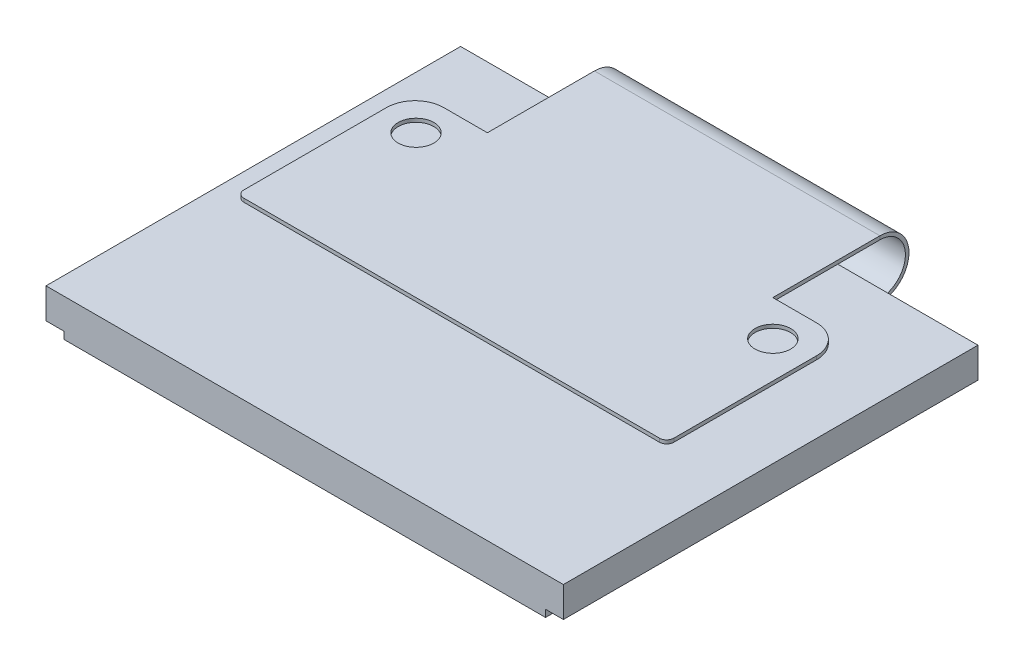
SolidWorks part; units mm, degrees
ref_plane "Front Plane" through (0, 0, 0) normal (0, 0, 1) x (1, 0, 0)
ref_plane "Top Plane" through (0, 0, 0) normal (0, 1, 0) x (1, 0, 0)
ref_plane "Right Plane" through (0, 0, 0) normal (1, 0, 0) x (0, 0, -1)
sketch "Sketch2" plane through (0, 0, 0) normal (0, 1, 0) x (1, 0, 0)
  line L1 (-7.25, 5.81) -> (7.25, 5.81)
  line L2 (-7.25, 5.81) -> (-7.25, -5.81)
  line L3 (-7.25, -5.81) -> (7.25, -5.81)
  line L4 (7.25, 5.81) -> (7.25, -5.81)
  line L5 (-7.25, 5.81) -> (7.25, -5.81) construction
  line L6 (-7.25, -5.81) -> (7.25, 5.81) construction
  point P0 (0, 0)
extrude "Boss-Extrude1" add sketch "Sketch2" along normal mid plane 0.85
sketch "Sketch6" plane through (0, -0.425, 0) normal (0, -1, 0) x (1, 0, 0)
  line L0 (-7.25, 5.81) -> (7.25, 5.81) construction
  line L1 (-6.75, 5.81) -> (6.75, 5.81)
  line L2 (-6.75, 5.81) -> (-6.75, -2.29)
  line L3 (-6.75, -2.29) -> (6.75, -2.29)
  line L4 (6.75, 5.81) -> (6.75, -2.29)
  line L5 (-6.75, 5.81) -> (6.75, -2.29) construction
  line L6 (-6.75, -2.29) -> (6.75, 5.81) construction
  point P0 (0, 1.76)
  dimension "D1" = 0
  dimension "D2" = 0
  dimension "D3" = 8.1
  dimension "D4" = 13.5
extrude "Boss-Extrude2" add sketch "Sketch6" along normal blind 0.2
sketch "Sketch7" plane through (0, -0.625, 0) normal (0, -1, 0) x (1, 0, 0)
  line L0 (6.75, 5.81) -> (-6.75, 5.81) construction
  line L1 (-6.29, 5) -> (6.29, 5)
  line L2 (-6.29, 5) -> (-6.29, -1.98)
  line L3 (-6.29, -1.98) -> (6.29, -1.98)
  line L4 (6.29, 5) -> (6.29, -1.98)
  line L5 (-6.29, 5) -> (6.29, -1.98) construction
  line L6 (-6.29, -1.98) -> (6.29, 5) construction
  line L7 (-6.75, 5.81) -> (-6.75, -2.29) construction
  line L8 (-6.75, -2.29) -> (6.75, -2.29) construction
  point P0 (0, 1.51)
  dimension "D1" = 0.81
  dimension "D2" = 0
  dimension "D3" = 0.46
  dimension "D4" = 0.31
extrude "Boss-Extrude3" add sketch "Sketch7" along normal blind 0.15
sketch "Sketch9" plane through (0, -0.425, 0) normal (0, -1, 0) x (1, 0, 0)
  line L1 (-6.096, -2.4527) -> (6.096, -2.4527)
  line L2 (-6.096, -2.4527) -> (-6.096, -4.9927)
  line L3 (-6.096, -4.9927) -> (-3.2893, -4.9927)
  line L4 (6.096, -2.4527) -> (6.096, -4.9927)
  line L5 (-6.096, -2.4527) -> (6.096, -4.9927) construction
  line L6 (-6.096, -4.9927) -> (6.096, -2.4527) construction
  line L7 (-6.75, -2.29) -> (6.75, -2.29) construction
  line L8 (-3.2893, -7.8563) -> (3.2893, -7.8563)
  line L9 (-3.2893, -4.9927) -> (-3.2893, -7.8563)
  line L10 (0, 0) -> (0, -4.9927) construction
  line L11 (3.2893, -4.9927) -> (3.2893, -7.8563)
  line L12 (3.2893, -4.9927) -> (6.096, -4.9927)
  line L13 (0, -7.8563) -> (0, -11.701) construction
  point P0 (0, -3.7227)
  point P11 (0, -7.8563)
  dimension "D1" = 0.1627
  dimension "D2" = 12.192
  dimension "D3" = 0
  dimension "D4" = 2.54
  dimension "D5" = 2.8636
  dimension "D6" = 6.5786
extrude "Boss-Extrude4" add sketch "Sketch9" along normal blind 0.1755
fillet "Fillet1" radius 0.762 2 edges at (6.096, -0.5127, -4.9927) (-6.096, -0.5127, -4.9927)
fillet "Fillet2" radius 0.2 2 edges at (3.2893, -0.5127, -7.8563) (-3.2893, -0.5127, -7.8563)
sketch "Sketch12" plane through (0, 0, 0) normal (1, 0, 0) x (0, 0, -1)
  line L0 (5.81, -0.425) -> (6.31, -0.425)
  line L2 (6.31, 1.205) -> (-1.69, 1.205)
  arc A1 (6.31, -0.425) -> (6.31, 1.205) centre (6.31, 0.39) ccw
  point P3 (7.125, 0.39)
  point P7 (6.31, 1.205)
  dimension "D2" = 1.63
  dimension "D3" = 8
  dimension "D1" = 0.5
sketch "Sketch13" plane through (0, 0, -5.81) normal (0, 0, -1) x (-1, 0, 0)
  line L0 (-3.2893, -0.425) -> (3.2893, -0.425) construction
  line L2 (-4, -0.425) -> (-4, -0.325)
  line L3 (-4, -0.325) -> (4, -0.325)
  line L4 (4, -0.425) -> (4, -0.325)
  line L5 (0, -0.425) -> (4, -0.325) construction
  line L6 (-4, -0.325) -> (0, -0.425) construction
  line L7 (-4, -0.425) -> (4, -0.425)
  point P0 (0, -0.425)
  dimension "D1" = 0.1
  dimension "D2" = 0
  dimension "D3" = 8
  dimension "D4" = 4
sweep "Sweep2" add profiles "Sketch13" path "Sketch12"
sketch "Sketch14" plane through (0, 1.205, 0) normal (0, 1, 0) x (1, 0, 0)
  line L1 (-4, -1.69) -> (-6.0249, -1.69)
  line L2 (-4, -1.69) -> (-4, 3.31)
  line L3 (-4, 3.31) -> (-6.0249, 3.31)
  line L4 (-6.0249, -1.69) -> (-6.0249, 3.31)
  line L5 (4, -1.69) -> (6.0249, -1.69)
  line L6 (4, -1.69) -> (4, 3.31)
  line L7 (4, 3.31) -> (6.0249, 3.31)
  line L8 (6.0249, -1.69) -> (6.0249, 3.31)
extrude "Boss-Extrude6" add sketch "Sketch14" against normal blind 0.1
sketch "Sketch17" plane through (0, 1.205, 0) normal (0, 1, 0) x (1, 0, 0)
  line L0 (6.0249, -1.69) -> (-6.0249, -1.69) construction
  circle A0 centre (-5, 2.31) radius 0.5
  circle A1 centre (5, 2.31) radius 0.5
  dimension "D3" = 1
  dimension "D4" = 1
  dimension "D1" = 5
  dimension "D2" = 5
  dimension "D5" = 4
  dimension "D6" = 4
extrude "Cut-Extrude3" cut sketch "Sketch17" against normal blind 0.1
fillet "Fillet3" radius 0.2 2 edges at (6.0249, 1.155, 1.69) (-6.0249, 1.155, 1.69)
fillet "Fillet4" radius 0.8 2 edges at (6.0249, 1.155, -3.31) (-6.0249, 1.155, -3.31)
